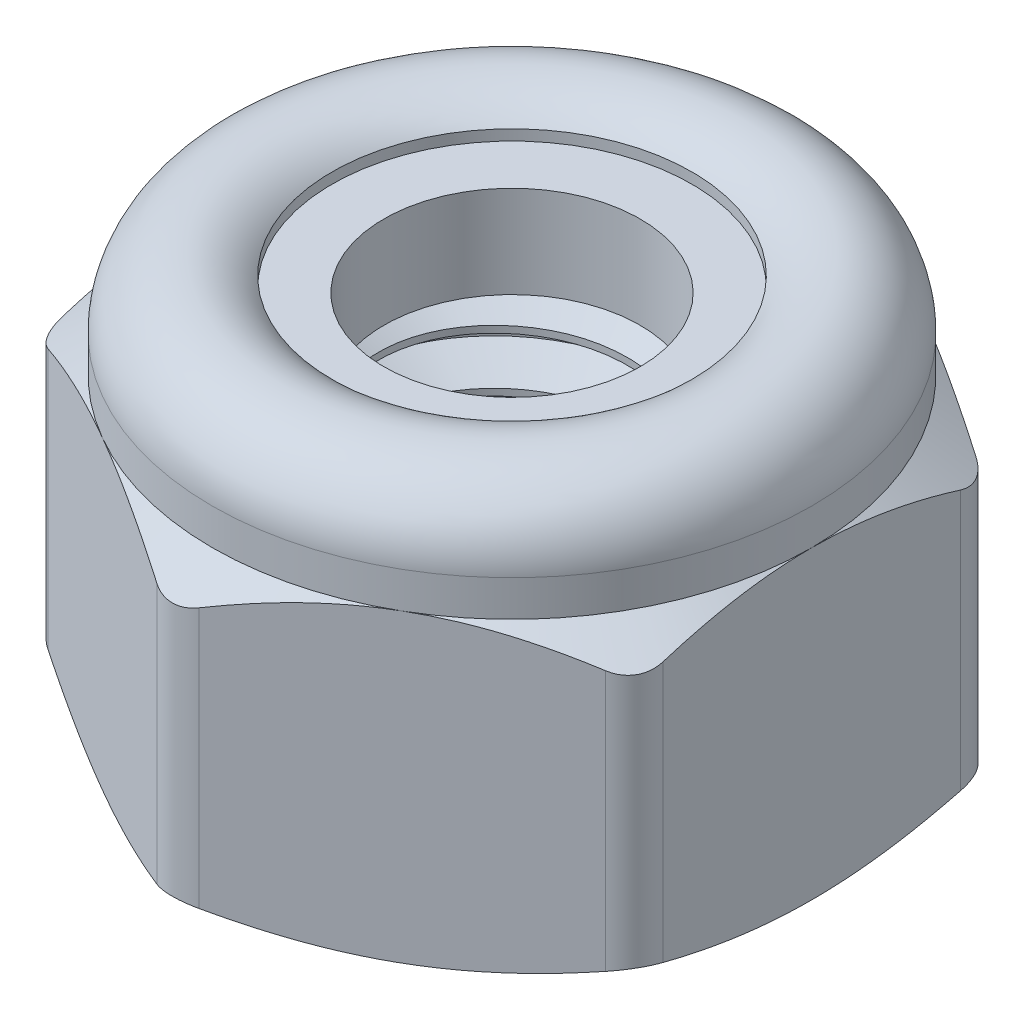
SolidWorks part; units mm, degrees
ref_plane "Front Plane" through (0, 0, 0) normal (0, 0, 1) x (1, 0, 0)
ref_plane "Top Plane" through (0, 0, 0) normal (0, 1, 0) x (1, 0, 0)
ref_plane "Right Plane" through (0, 0, 0) normal (1, 0, 0) x (0, 0, -1)
sketch "Sketch1" plane through (0, 0, 0) normal (0, 0, 1) x (1, 0, 0)
  line L0 (0, -1.95) -> (0, 1.95) construction
  line L1 (2.75, 0) -> (-2.75, 0) construction
  line L2 (1.5, -1.95) -> (-1.5, -1.95) construction
  line L3 (1.5, -1.95) -> (1.5, -1.45) construction
  point P4 (0, 0)
  point P8 (0, 0)
  point P11 (0, -1.95)
  dimension "Height" = 3.9
  dimension "Width" = 5.5
  dimension "Thread Size" = 3
  dimension "Thread Pitch" = 0.5
sketch "Sketch2" plane through (0, 0, 0) normal (0, 1, 0) x (1, 0, 0)
  line L0 (-1.5, 0.2187) -> (-1.5, -0.2187) construction
  line L1 (0, 3.1754) -> (-2.75, 1.5877)
  line L2 (-2.75, 1.5877) -> (-2.75, -1.5877)
  line L3 (-2.75, -1.5877) -> (0, -3.1754)
  line L4 (0, -3.1754) -> (2.75, -1.5877)
  line L5 (2.75, -1.5877) -> (2.75, 1.5877)
  line L6 (2.75, 1.5877) -> (0, 3.1754)
  line L7 (-1.5, -0.2187) -> (-1.1752, -0.0313) construction
  line L8 (-1.1752, -0.0313) -> (-1.1752, 0.0312) construction
  line L9 (-1.1752, 0.0312) -> (-1.5, 0.2187) construction
  line L10 (-1.1752, 0) -> (-1.5, 0) construction
  line L11 (-1.3376, 0.125) -> (-1.3376, -0.125) construction
  line L12 (1.5, 0) -> (-1.5, 0) construction
  line L13 (2.75, 0) -> (-2.75, 0) construction
  circle A0 centre (0, 0) radius 2.75 construction
  circle A1 centre (0, 0) radius 1.1752
  point P19 (0, -1.1752)
  dimension "D1" = 0.0625
  dimension "D2" = 0.25
  dimension "D3" = 60
extrude "Boss-Extrude1" add sketch "Sketch2" along normal up to vertex (1.95 mm away) and the other way up to vertex (1.95 mm away) up to point (0, 1.95, 0) other way up to point (0, -1.95, 0)
fillet "Fillet1" radius 0.385 6 edges at (-2.75, 0, -1.5877) (0, 0, -3.1754) (-2.75, 0, 1.5877) (2.75, 0, -1.5877) (2.75, 0, 1.5877) (0, 0, 3.1754)
sketch "Sketch3" plane through (0, 0, 0) normal (1, 0, 0) x (0, 0, -1)
  line L0 (3.1754, 0.975) -> (3.1754, 2.95)
  line L1 (1.65, 0.78) -> (2.75, 0.78) construction
  line L2 (2.53, -1.95) -> (3.1754, -1.5774)
  line L3 (1.6989, -1.95) -> (3.0643, -1.95) construction
  line L4 (3.1754, 1.95) -> (3.1754, -1.95) construction
  line L5 (3.1754, -1.5774) -> (3.1754, -1.95)
  line L6 (3.1754, -1.95) -> (2.53, -1.95)
  line L7 (2.75, 0.975) -> (3.1754, 0.6771)
  line L8 (3.1754, 0.6771) -> (3.1754, 0.975)
  line L9 (2.75, 0.78) -> (2.75, 0.975) construction
  line L10 (1.6989, -1.95) -> (3.0643, -1.95) construction
  line L11 (2.75, 0.975) -> (2.75, 1.3056)
  line L12 (1.6989, 1.95) -> (3.0643, 1.95) construction
  line L13 (1.1752, 0.78) -> (1.65, 0.78)
  line L14 (1.65, 0.78) -> (1.65, 1.7613)
  line L16 (1.65, 1.7613) -> (2.1056, 1.3056) construction
  line L17 (2.1056, 1.3056) -> (2.1056, 1.95) construction
  line L18 (1.1752, 0.78) -> (1.1752, 2.95)
  line L19 (1.1752, 2.95) -> (3.1754, 2.95)
  line L21 (1.1752, -1.95) -> (1.1752, -1.65)
  line L22 (-1.3654, -1.95) -> (1.3654, -1.95) construction
  line L24 (1.4752, -1.95) -> (1.1752, -1.95)
  line L25 (1.1752, -1.65) -> (1.4752, -1.95)
  line L26 (0, 1.95) -> (0, -1.95) construction
  line L27 (-1.3654, 1.95) -> (1.3654, 1.95) construction
  line L28 (-1.3654, -1.95) -> (1.3654, -1.95) construction
  arc A0 (2.75, 1.3056) -> (1.65, 1.7613) centre (2.1056, 1.3056) ccw
  point P0 (2.75, 0.975)
  point P1 (2.75, 0)
  point P14 (1.1752, 0)
  point P36 (2.75, -1.95)
  dimension "D1" = 2.925
  dimension "D2" = 30
  dimension "D3" = 45
  dimension "D4" = 1
  dimension "D5" = 0.3
  dimension "D6" = 2.73
  dimension "D7" = 0.22
  dimension "D8" = 35
  dimension "D9" = 3.3
revolve "Cut-Revolve2" cut sketch "Sketch3" angle 360 about L0
sketch "Sketch12" plane through (0, 0, 0) normal (1, 0, 0) x (0, 0, -1)
  line L0 (2.1056, 1.3056) -> (2.1056, 1.95) construction
  line L1 (1.65, 0.78) -> (2.1056, 0.78)
  line L2 (1.65, 0.78) -> (1.65, 1.6638)
  line L3 (1.65, 1.6638) -> (2.1056, 1.6638)
  line L4 (2.1056, 0.78) -> (2.1056, 1.6638)
  dimension "D1" = 0.0975
revolve "Cut-Revolve3" cut sketch "Sketch12" angle 360 about L26
sketch "Sketch4" plane through (0, 0, 0) normal (1, 0, 0) x (0, 0, -1)
  line L1 (1.1752, 0.78) -> (2.1056, 0.78)
  line L2 (1.1752, 0.78) -> (1.1752, 1.6248)
  line L3 (1.1752, 1.6248) -> (2.1056, 1.6248)
  line L4 (2.1056, 0.78) -> (2.1056, 1.6248)
  line L5 (1.65, 1.7613) -> (-1.65, 1.7613) construction
  line L7 (2.1056, 1.3056) -> (2.1056, 1.95) construction
  dimension "D1" = 0.1365
revolve "Revolve1" add sketch "Sketch4" angle 360 about L0
sketch "Sketch5" plane through (0, 0, 0) normal (0, 1, 0) x (1, 0, 0)
  circle A0 centre (0, 0) radius 1.1752 construction
  point P0 (0, -1.1752)
sketch "Sketch6" plane through (0, 0, 0) normal (1, 0, 0) x (0, 0, -1)
  line L0 (1.4752, 0.78) -> (1.4752, -1.95)
  line L3 (1.4752, -1.95) -> (0, -1.95)
  line L4 (0, -1.95) -> (0, 0.78)
  line L5 (0, -1.95) -> (0, 1.95) construction
  line L6 (0, 0.78) -> (1.4752, 0.78)
  line L7 (-1.4752, -1.95) -> (1.4752, -1.95) construction
  line L9 (1.1752, 0.78) -> (1.65, 0.78) construction
revolve "Revolve2" add sketch "Sketch6" angle 360 about L4
sketch "Sketch7" plane through (0, -1.95, 0) normal (0, -1, 0) x (1, 0, 0)
  circle A2 centre (0, 0) radius 1.4752
  circle A3 centre (0, 0) radius 1.4752
  dimension "D1" = 0
curve "Helix/Spiral1" pitch 0.5 height 3.9 turns 7.8
sketch "Sketch8" plane through (0, 0, 0) normal (0, 0, 1) x (1, 0, 0)
  line L0 (1.5294, -1.9187) -> (1.0964, -2.1687) construction
  line L1 (1.0964, -2.1687) -> (1.5294, -2.4187) construction
  line L2 (1.5294, -2.4187) -> (1.5294, -1.9187) construction
  line L3 (1.1505, -2.1375) -> (1.1505, -2.2)
  line L4 (1.4752, -1.95) -> (1.4752, -2.3875) construction
  line L5 (1.4752, -2.1687) -> (1.5294, -2.1687) construction
  line L6 (1.0964, -2.1687) -> (1.1505, -2.1687) construction
  line L7 (1.5023, -2.1687) -> (1.5023, -2.4031) construction
  line L8 (1.1505, -2.1375) -> (1.5294, -1.9187)
  line L9 (1.5294, -1.9187) -> (1.5023, -2.4031)
  line L10 (1.1505, -2.2) -> (1.5023, -2.4031)
  dimension "D1" = 0.5
  dimension "D2" = 0.0625
sweep "Cut-Sweep1" cut profiles "Sketch8" path "Helix/Spiral1"
sketch "Sketch9" plane through (0, 0, 0) normal (0, 0, 1) x (1, 0, 0)
  line L5 (0, -0.45) -> (0, -1.95)
  line L6 (0, -1.95) -> (1.5, -1.95)
  line L7 (1.5, -1.95) -> (0, -0.45)
revolve "Revolve3" add sketch "Sketch9" angle 360 about L5
sketch "Sketch10" plane through (0, -1.95, 0) normal (0, -1, 0) x (1, 0, 0)
  circle A0 centre (0, 0) radius 1.4752 construction
  circle A1 centre (0, 0) radius 1.4752
extrude "Boss-Extrude2" add sketch "Sketch10" against normal up to surface (2.73 mm away)
combine bodies "Combine1" bodies to combine 110 109
equation "\"D1@Sketch3\"=\"Height@Sketch1\" *.75"
equation "\"D5@Sketch3\"=\"Thread Size@Sketch1\"*.1"
equation "\"D4@Helix/Spiral1\"=\"Thread Pitch@sketch1\""
equation "\"D3@Helix/Spiral1\"=\"Height@sketch1\""
equation "\"D1@Sketch8\"=\"Thread Pitch@sketch1\""
equation "\"D2@Sketch8\"=\"Thread Pitch@sketch1\"/8"
equation "\"D1@Sketch2\"=\"Thread Pitch@sketch1\"/8"
equation "\"D2@Sketch2\"=\"Thread Pitch@sketch1\"/2"
equation "\"D1@Sketch4\"=\"Height@Sketch1\" * .035"
equation "\"D1@Fillet1\"=\"Width@Sketch1\" * .07"
equation "\"D6@Sketch3\"=\"Height@Sketch1\" *.7"
equation "\"D7@Sketch3\"=\"Width@Sketch1\"*.04"
equation "\"D9@Sketch3\"=\"Thread Size@Sketch1\"*1.1"
equation "\"D1@Sketch12\"=\"Height@Sketch1\" * .025"
